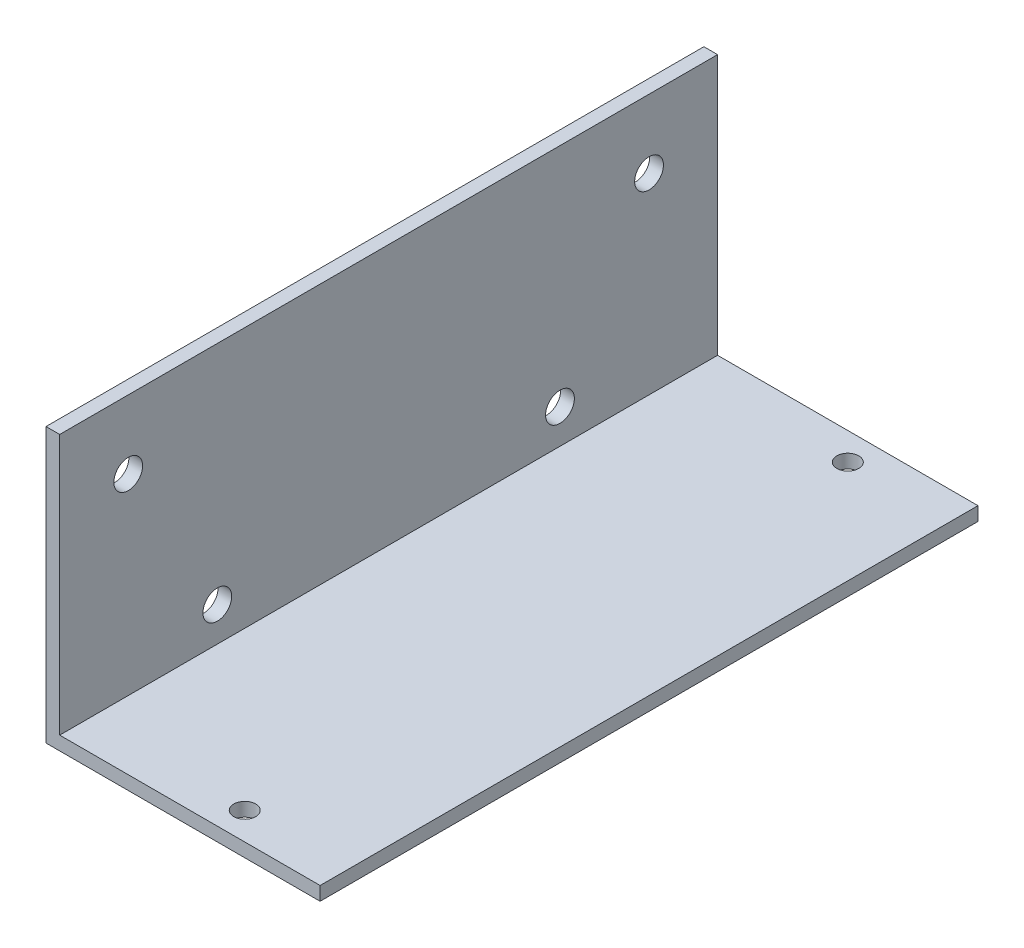
SolidWorks part; units mm, degrees
material "1060 Сплав"
ref_plane "Спереди" through (0, 0, 0) normal (0, 0, 1) x (1, 0, 0)
ref_plane "Сверху" through (0, 0, 0) normal (0, 1, 0) x (1, 0, 0)
ref_plane "Справа" through (0, 0, 0) normal (1, 0, 0) x (0, 0, -1)
sketch "Эскиз1" plane through (0, 0, 0) normal (0, 0, 1) x (1, 0, 0)
  line L0 (0, 0) -> (40, 0)
  line L1 (40, 0) -> (40, 2)
  line L2 (40, 2) -> (2, 2)
  line L3 (2, 2) -> (2, 40)
  line L4 (2, 40) -> (0, 40)
  line L5 (0, 40) -> (0, 0)
  dimension "D1" = 40
  dimension "D2" = 2
  dimension "D3" = 40
extrude "Бобышка-Вытянуть1" add sketch "Эскиз1" along normal blind 96
sketch "Эскиз2" plane through (0, 0, 0) normal (0, -1, 0) x (1, 0, 0)
  line L0 (40, 96) -> (40, 0) construction
  line L3 (0, 0) -> (40, 0) construction
  line L4 (25, 4) -> (25, 96) construction
  line L5 (0, 96) -> (40, 96) construction
  circle A1 centre (25, 92) radius 1.6
  circle A2 centre (25, 4) radius 1.6
  dimension "D1" = 15
  dimension "D2" = 4
  dimension "D3" = 3.2
  dimension "D4" = 3.2
  dimension "D5" = 4
extrude "Вырез-Вытянуть1" cut sketch "Эскиз2" against normal through all
sketch "Эскиз3" plane through (0, 0, 0) normal (-1, 0, 0) x (0, 0, 1)
  line L0 (0, 30) -> (96, 30) construction
  line L1 (96, 40) -> (0, 40) construction
  line L3 (0, 40) -> (0, 0) construction
  line L4 (96, 40) -> (96, 0) construction
  line L5 (96, 7) -> (0, 7) construction
  line L6 (96, 0) -> (0, 0) construction
  circle A0 centre (10, 30) radius 2.1
  circle A1 centre (86, 30) radius 2.1
  circle A2 centre (73, 7) radius 2.1
  circle A3 centre (23, 7) radius 2.1
  point P16 (48, 7)
  dimension "D1" = 4.2
  dimension "D2" = 10
  dimension "D3" = 10
  dimension "D4" = 10
  dimension "D6" = 4.2
  dimension "D7" = 50
  dimension "D8" = 25
  dimension "D5" = 7
extrude "Вырез-Вытянуть2" cut sketch "Эскиз3" against normal through all
equation "\"3ю2\"=3.4952"
